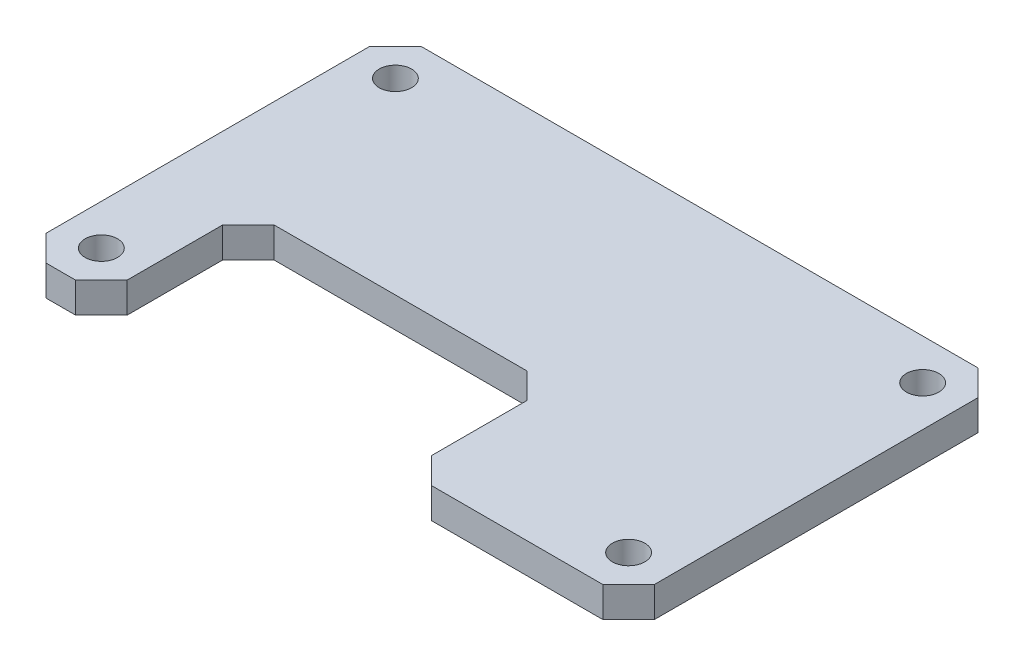
SolidWorks part; units mm, degrees
ref_plane "Front Plane" through (0, 0, 0) normal (0, 0, 1) x (1, 0, 0)
ref_plane "Top Plane" through (0, 0, 0) normal (0, 1, 0) x (1, 0, 0)
ref_plane "Right Plane" through (0, 0, 0) normal (1, 0, 0) x (0, 0, -1)
sketch "Sketch1" plane through (0, 0, 0) normal (0, 1, 0) x (1, 0, 0)
  line L1 (-30, -18.5) -> (30, -18.5)
  line L2 (-30, -18.5) -> (-30, 18.5)
  line L3 (-30, 18.5) -> (30, 18.5)
  line L4 (30, -18.5) -> (30, 18.5)
  line L5 (-30, -18.5) -> (30, 18.5) construction
  line L6 (-30, 18.5) -> (30, -18.5) construction
  point P0 (0, 0)
  dimension "D1" = 37
  dimension "D2" = 60
extrude "Boss-Extrude1" add sketch "Sketch1" along normal blind 2.9972
sketch "Sketch2" plane through (0, 2.9972, 0) normal (0, 1, 0) x (1, 0, 0)
  line L0 (30, 18.5) -> (-30, 18.5) construction
  line L1 (-26, 14.5) -> (26, 14.5) construction
  line L2 (-26, 14.5) -> (-26, -14.5) construction
  line L3 (-26, -14.5) -> (26, -14.5) construction
  line L4 (26, 14.5) -> (26, -14.5) construction
  line L5 (-26, 14.5) -> (26, -14.5) construction
  line L6 (-26, -14.5) -> (26, 14.5) construction
  line L7 (30, -18.5) -> (30, 18.5) construction
  line L8 (-30, -18.5) -> (30, -18.5) construction
  line L9 (-30, 18.5) -> (-30, -18.5) construction
  circle A0 centre (-26, 14.5) radius 1.6
  circle A1 centre (-26, -14.5) radius 1.6
  circle A2 centre (26, -14.5) radius 1.6
  circle A3 centre (26, 14.5) radius 1.6
  point P12 (0, 0)
  dimension "D1" = 3.2
  dimension "D2" = 4
  dimension "D3" = 4
  dimension "D4" = 4
  dimension "D5" = 4
extrude "Cut-Extrude1" cut sketch "Sketch2" against normal through all
sketch "Sketch3" plane through (0, 2.9972, 0) normal (0, 1, 0) x (1, 0, 0)
  line L0 (8, -4) -> (30, -4) construction
  line L1 (-22, -4) -> (8, -4)
  line L2 (-22, -4) -> (-22, -18.5)
  line L3 (-22, -18.5) -> (8, -18.5)
  line L4 (8, -4) -> (8, -18.5)
  line L5 (-22, -4) -> (8, -18.5) construction
  line L6 (-22, -18.5) -> (8, -4) construction
  line L7 (-30, -18.5) -> (30, -18.5) construction
  line L8 (30, -18.5) -> (30, 18.5) construction
  line L9 (-22, -4) -> (-30, -4) construction
  line L10 (-30, 18.5) -> (-30, -18.5) construction
  circle A0 centre (-26, -14.5) radius 1.6 construction
  point P0 (-7, -11.25)
  dimension "D3" = 4
  dimension "D1" = 30
  dimension "D2" = 4
extrude "Cut-Extrude2" cut sketch "Sketch3" against normal through all
chamfer "Chamfer1" distance 2.54 angle 45 8 edges at (-30, 1.4986, -18.5) (30, 1.4986, -18.5) (30, 1.4986, 18.5) (8, 1.4986, 18.5) (-30, 1.4986, 18.5) (-22, 1.4986, 18.5) (8, 1.4986, 4) (-22, 1.4986, 4)
